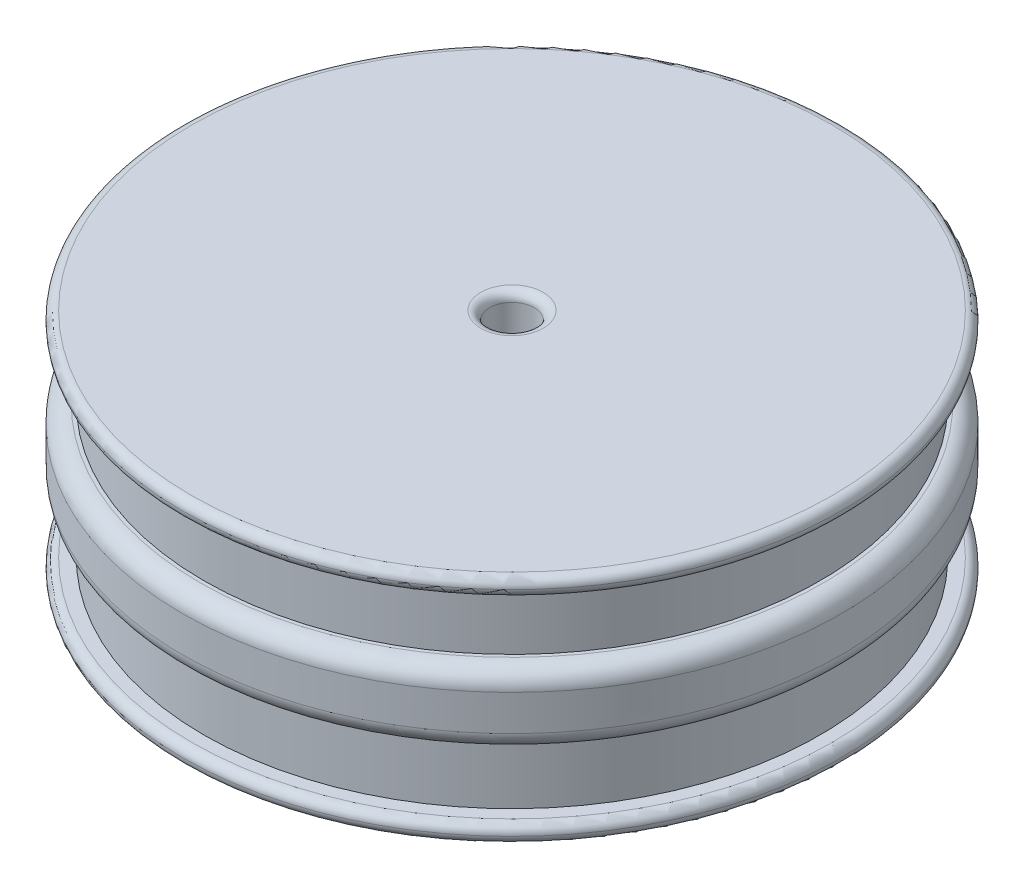
SolidWorks part; units mm, degrees
ref_plane "Front Plane" through (0, 0, 0) normal (0, 0, 1) x (1, 0, 0)
ref_plane "Top Plane" through (0, 0, 0) normal (0, 1, 0) x (1, 0, 0)
ref_plane "Right Plane" through (0, 0, 0) normal (1, 0, 0) x (0, 0, -1)
sketch "Sketch1" plane through (0, 0, 0) normal (0, 1, 0) x (1, 0, 0)
  circle A0 centre (0, 0) radius 18.5
  circle A1 centre (0, 0) radius 1.25
  dimension "D1" = 2.5
  dimension "D2" = 37
extrude "Boss-Extrude1" add sketch "Sketch1" along normal blind 13
sketch "Sketch3" plane through (0, 0, 0) normal (1, 0, 0) x (0, 0, -1)
  line L0 (-18.5, 13) -> (-18.5, 0) construction
  line L1 (-18.5, 12) -> (-17.3, 12)
  line L2 (-18.5, 12) -> (-18.5, 8.5)
  line L3 (-18.5, 8.5) -> (-17.3, 8.5)
  line L4 (-17.3, 12) -> (-17.3, 8.5)
  line L7 (-18.5, 4.5) -> (-17.3, 4.5)
  line L8 (-18.5, 4.5) -> (-18.5, 1)
  line L9 (-18.5, 1) -> (-17.3, 1)
  line L10 (-17.3, 4.5) -> (-17.3, 1)
  line L11 (20.35, 0) -> (-20.35, 0) construction
  line L12 (18.5, 13) -> (-18.5, 13) construction
  line L13 (0, -0.5434) -> (0, 15.7056) construction
  line L14 (0, 7.15) -> (0, -7.15) construction
  dimension "D1" = 1
  dimension "D2" = 3.5
  dimension "D3" = 1
  dimension "D4" = 1.2
revolve "Cut-Revolve1" cut sketch "Sketch3" angle 360 about L13
fillet "Fillet1" radius 1 2 edges at (0, 4.5, -18.5) (0, 8.5, -18.5)
fillet "Fillet2" radius 0.5 2 edges at (0, 12, -18.5) (0, 1, -18.5)
fillet "Fillet3" radius 0.5 2 edges at (0, 0, 18.5) (0, 13, 18.5)
fillet "Fillet4" radius 0.5 2 edges at (0, 0, 1.25) (0, 13, 1.25)
